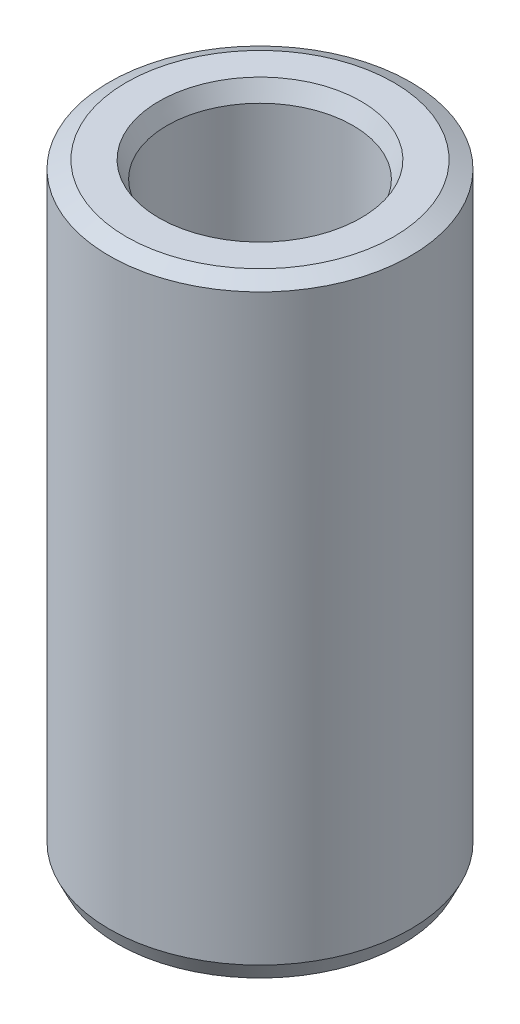
SolidWorks part; units mm, degrees
ref_plane "Front Plane" through (0, 0, 0) normal (0, 0, 1) x (1, 0, 0)
ref_plane "Top Plane" through (0, 0, 0) normal (0, 1, 0) x (1, 0, 0)
ref_plane "Right Plane" through (0, 0, 0) normal (1, 0, 0) x (0, 0, -1)
sketch "Sketch1" plane through (0, 0, 0) normal (0, 1, 0) x (1, 0, 0)
  circle A0 centre (0, 0) radius 57.5
  dimension "SLEEVE_OD" = 115
extrude "Boss-Extrude1" add sketch "Sketch1" along normal blind 232.1214
sketch "Sketch2" plane through (0, 0, 0) normal (0, 1, 0) x (1, 0, 0)
  circle A0 centre (0, 0) radius 35.4831
  dimension "BORE_D" = 70.9662
extrude "Cut-Extrude1" cut sketch "Sketch2" along normal through all
chamfer "Chamfer1" distance 3.1032 angle 64.33 4 edges at (0, 232.1214, 35.4831) (0, 0, 35.4831) (0, 0, 57.5) (0, 232.1214, 57.5) first distance on face at (0, 232.1214, 35.4831) first distance on face at (0, 0, 35.4831) first distance on face at (0, 232.1214, 57.5)
